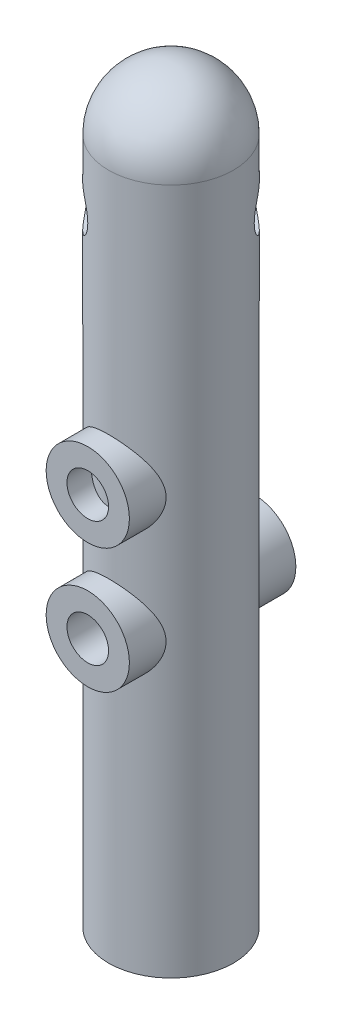
SolidWorks part; units mm, degrees
ref_plane "Front Plane" through (0, 0, 0) normal (0, 0, 1) x (1, 0, 0)
ref_plane "Top Plane" through (0, 0, 0) normal (0, 1, 0) x (1, 0, 0)
ref_plane "Right Plane" through (0, 0, 0) normal (1, 0, 0) x (0, 0, -1)
sketch "Sketch1" plane through (0, 0, 0) normal (0, 1, 0) x (1, 0, 0)
  circle A0 centre (0, 0) radius 1.5
  dimension "D1" = 3
extrude "Boss-Extrude1" add sketch "Sketch1" along normal blind 18
fillet "Fillet1" radius 1.5 1 edges at (0, 18, 1.5)
sketch "Sketch2" plane through (0, 0, 0) normal (0, 0, 1) x (1, 0, 0)
  circle A0 centre (0, 7) radius 1
  circle A1 centre (0, 10) radius 1
  dimension "D1" = 2
  dimension "D2" = 7
  dimension "D3" = 10
extrude "Extrude-Thin1" add sketch "Sketch2" along normal blind 2 thin thin type one direction reverse wall 0.5
extrude "Extrude-Thin2" add sketch "Sketch2<2>" against normal blind 2 thin contours A0 thin type one direction reverse wall 0.5
sketch "Sketch2<2>" plane through (0, 0, 0) normal (0, 0, 1) x (1, 0, 0) same geometry as "Sketch2"
sketch "Sketch3" plane through (0, 0, 0) normal (0, 0, 1) x (1, 0, 0)
  circle A0 centre (0, 7) radius 0.5 construction
  circle A1 centre (0, 7) radius 0.5
extrude "Cut-Extrude1" cut sketch "Sketch3" against normal through all both and the other way through all
ref_plane "Plane1" through (0, 0, 0) normal (-0.7071, 0, 0.7071) x (0.7071, 0, 0.7071)
sketch "Sketch4" plane through (0, 0, 0) normal (-0.7071, 0, 0.7071) x (0.7071, 0, 0.7071)
  line L0 (1.5, 16.5) -> (-1.5, 16.5) construction
  circle A0 centre (0, 15) radius 0.5
  dimension "D1" = 1
  dimension "D2" = 1.5
extrude "Cut-Extrude2" cut sketch "Sketch4" against normal mid plane 6
sketch "Sketch5" plane through (0, 0, 0) normal (0, -1, 0) x (1, 0, 0)
  circle A0 centre (0, 0) radius 0.75
  dimension "D1" = 1.5
extrude "Cut-Extrude3" cut sketch "Sketch5" against normal blind 17
